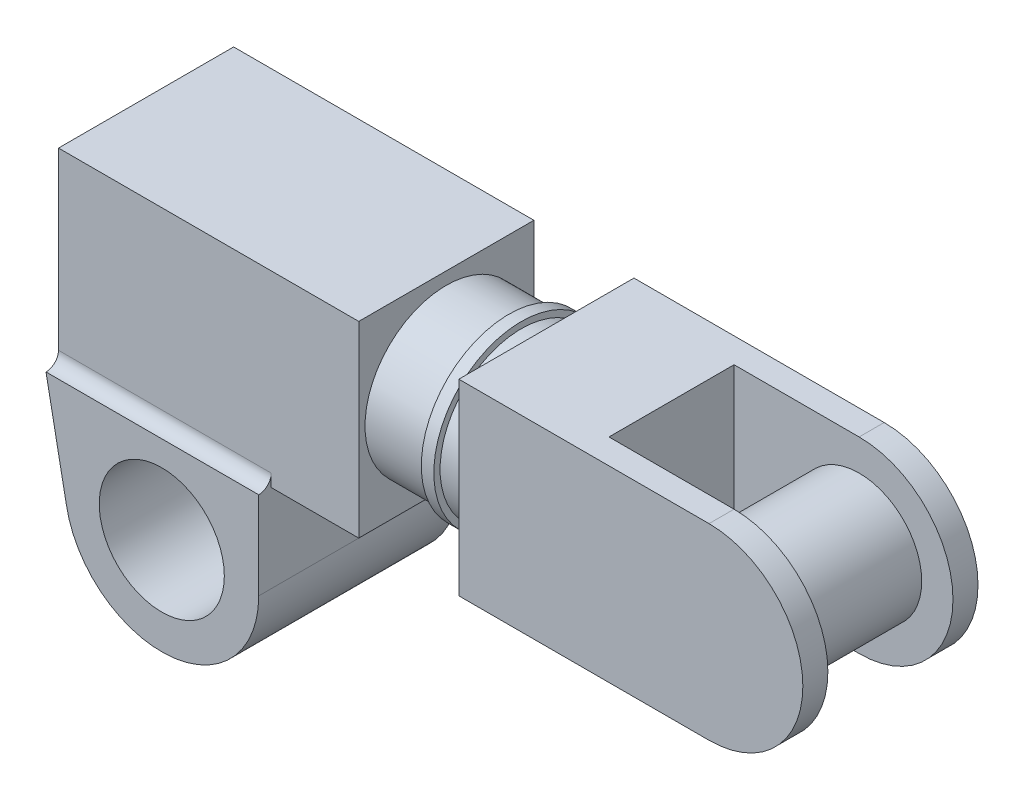
SolidWorks part; units mm, degrees
material "ABS"
ref_plane "Front Plane" through (0, 0, 0) normal (0, 0, 1) x (1, 0, 0)
ref_plane "Top Plane" through (0, 0, 0) normal (0, 1, 0) x (1, 0, 0)
ref_plane "Right Plane" through (0, 0, 0) normal (1, 0, 0) x (0, 0, -1)
sketch "Sketch2" plane through (0, 0, 0) normal (1, 0, 0) x (0, 0, -1)
  line L1 (70, -75) -> (-70, -75)
  line L2 (70, -75) -> (70, 75)
  line L3 (70, 75) -> (-70, 75)
  line L4 (-70, -75) -> (-70, 75)
  line L5 (70, -75) -> (-70, 75) construction
  line L6 (70, 75) -> (-70, -75) construction
  point P0 (0, 0)
  dimension "D1" = 140
  dimension "D2" = 150
extrude "Boss-Extrude1" add sketch "Sketch2" along normal blind 240
sketch "Sketch3" plane through (240, 0, 0) normal (1, 0, 0) x (0, 0, -1)
  circle A0 centre (0, 0) radius 65
  dimension "D1" = 130
extrude "Boss-Extrude2" add sketch "Sketch3" along normal blind 50
sketch "Sketch4" plane through (290, 0, 0) normal (1, 0, 0) x (0, 0, -1)
  circle A0 centre (0, 0) radius 70
  dimension "D1" = 140
extrude "Boss-Extrude3" add sketch "Sketch4" along normal blind 10
sketch "Sketch5" plane through (0, 0, 0) normal (0, 0, 1) x (1, 0, 0)
  line L0 (170.0448, -145) -> (170.0448, -75)
  line L5 (240, -75) -> (0, -75) construction
  line L6 (16.2188, -158.4383) -> (0, -75)
  line L7 (0, 75) -> (0, -75) construction
  line L8 (170.0448, -75) -> (0, -75)
  arc A4 (16.2188, -158.4383) -> (170.0448, -145) centre (92.5448, -145) ccw
  circle A5 centre (92.5448, -145) radius 50
  dimension "D1" = 155
  dimension "D4" = 85
  dimension "D3" = 191
  dimension "D5" = 100
  dimension "D2" = 70
extrude "Boss-Extrude4" add sketch "Sketch5" along normal mid plane 160
fillet "Fillet1" radius 10 2 edges at (85.0224, -75, -70) (85.0224, -75, 70)
sketch "Sketch6" plane through (300, 0, 0) normal (1, 0, 0) x (0, 0, -1)
  circle A0 centre (0, 0) radius 65
  dimension "D1" = 130
extrude "Boss-Extrude5" add sketch "Sketch6" along normal blind 20
sketch "Sketch7" plane through (0, 0, 0) normal (0, 0, 1) x (1, 0, 0)
  line L0 (520, -75) -> (320, -75)
  line L1 (320, -75) -> (320, 75)
  line L2 (320, 75) -> (520, 75)
  line L3 (320, -65) -> (320, 65) construction
  arc A0 (520, -75) -> (520, 75) centre (520, 0) ccw
  dimension "D1" = 150
  dimension "D2" = 200
extrude "Boss-Extrude6" add sketch "Sketch7" along normal mid plane 140
sketch "Sketch8" plane through (0, 0, 0) normal (0, 0, 1) x (1, 0, 0)
  line L0 (520, 75) -> (420, 75)
  line L1 (520, 75) -> (320, 75) construction
  line L2 (420, 75) -> (420, -75)
  line L3 (320, -75) -> (520, -75) construction
  line L4 (420, -75) -> (520, -75)
  arc A0 (520, -75) -> (520, 75) centre (520, 0) ccw construction
  arc A1 (520, -75) -> (520, 75) centre (520, 0) ccw
  dimension "D1" = 100
extrude "Cut-Extrude1" cut sketch "Sketch8" against normal mid plane 100
sketch "Sketch9" plane through (0, 0, -50) normal (0, 0, 1) x (1, 0, 0)
  circle A0 centre (520, 0) radius 50
  dimension "D1" = 100
extrude "Boss-Extrude7" add sketch "Sketch9" along normal up to next
ref_point "Point1"
